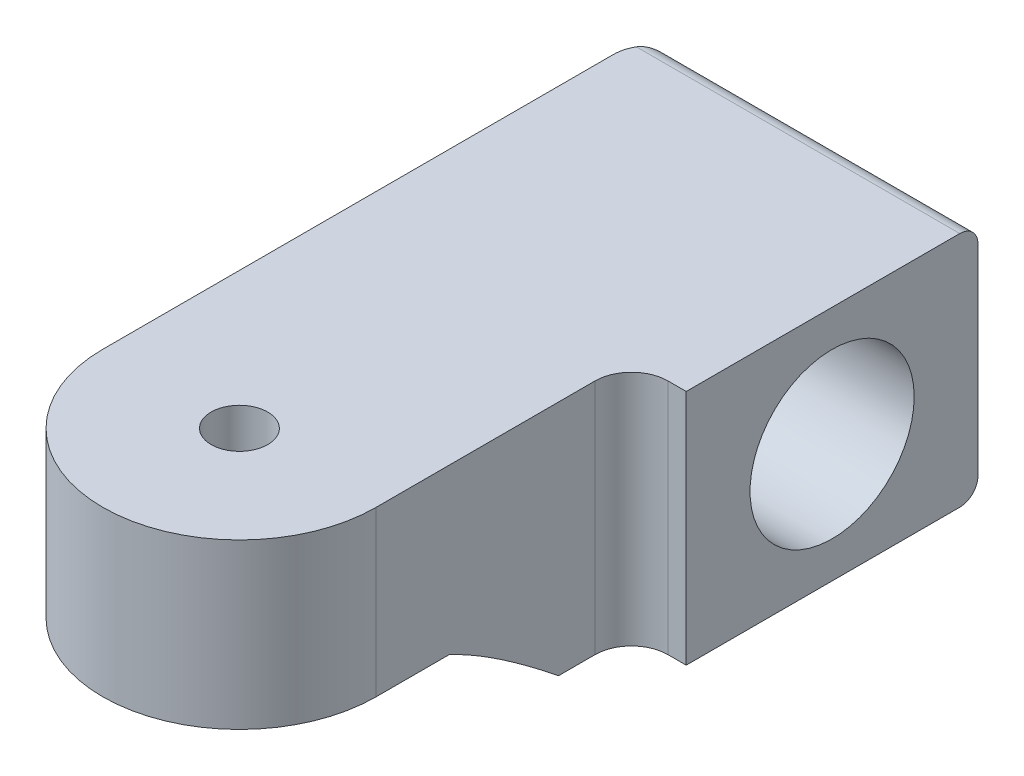
SolidWorks part; units mm, degrees
material "ABS"
ref_plane "前视基准面" through (0, 0, 0) normal (0, 0, 1) x (1, 0, 0)
ref_plane "上视基准面" through (0, 0, 0) normal (0, 1, 0) x (1, 0, 0)
ref_plane "右视基准面" through (0, 0, 0) normal (1, 0, 0) x (0, 0, -1)
sketch "Sketch1" plane through (0, 0, 0) normal (0, 1, 0) x (1, 0, 0)
  line L0 (0, 0) -> (0, 16)
  line L1 (0, 16) -> (-16, 16)
  line L2 (-18, 14) -> (-18, -14)
  line L3 (-18, -14) -> (-3, -14)
  line L4 (-3, -14) -> (-3, -2)
  line L5 (-1, 0) -> (0, 0)
  arc A0 (-3, -2) -> (-1, 0) centre (-1, -2) cw
  arc A1 (-16, 16) -> (-18, 14) centre (-16, 14) ccw
  circle A2 centre (-10.5, -14) radius 7.5
  circle A3 centre (-10.5, -14) radius 1.55
  point P9 (-3, 0)
  point P12 (-18, 16)
  dimension "D5" = 2
  dimension "D6" = 3.1
  dimension "D1" = 16
  dimension "D2" = 18
  dimension "D3" = 30
  dimension "D4" = 3
extrude "Boss-Extrude1" add sketch "Sketch1" along normal mid plane 13 contours A2 L4 A0 L5 L0 L1 A1 L2 region at (-9.414, 0, -4.3355)
extrude "Boss-Extrude2" add sketch "Sketch1<4>" against normal blind 9 from surface contours L3 A2 | L3 A2 region at (-10.5, 0, 17.2958) region at (-10.5, 0, 10.7042) starting at face at (-7.4786, 6.5, -3.0411)
sketch "Sketch1<4>" plane through (0, 0, 0) normal (0, 1, 0) x (1, 0, 0) same geometry as "Sketch1"
sketch "Sketch2" plane through (0, 0, 0) normal (1, 0, 0) x (0, 0, -1)
  line L0 (0, 6.5) -> (16, -6.5)
  circle A0 centre (8, 0) radius 4.5
  dimension "D1" = 9
extrude "Cut-Extrude1" cut sketch "Sketch2" against normal blind 15 contours L0 A0 | L0 A0 region at (0, 1.4823, -9.2043) region at (0, -1.4823, -6.7957)
chamfer "Chamfer1" distance 5 angle 45 1 edges at (-10.5, -6.5, 6.5)
fillet "Fillet1" radius 1 2 edges at (-8, -6.5, -16) (-8, 6.5, -16) tangent propagation no
sketch "Sketch3" plane through (0, -2.5, 0) normal (0, -1, 0) x (1, 0, 0)
  line L144 (-7.4777, 13.9234) -> (-8.0059, 15.1102)
  line L145 (-8.0059, 15.1102) -> (-8.5342, 16.2969)
  line L146 (-8.9225, 16.5791) -> (-10.2144, 16.715)
  line L147 (-10.2144, 16.715) -> (-11.5063, 16.8509)
  line L148 (-11.9448, 16.6557) -> (-12.7085, 15.6049)
  line L149 (-12.7085, 15.6049) -> (-13.4721, 14.554)
  line L150 (-13.5223, 14.0766) -> (-12.9941, 12.8898)
  line L151 (-12.9941, 12.8898) -> (-12.4658, 11.7031)
  line L152 (-12.0775, 11.4209) -> (-10.7856, 11.285)
  line L153 (-10.7856, 11.285) -> (-9.4937, 11.1491)
  line L154 (-9.0552, 11.3443) -> (-8.2915, 12.3951)
  line L155 (-8.2915, 12.3951) -> (-7.5279, 13.446)
  arc A63 (-7.5279, 13.446) -> (-7.4777, 13.9234) centre (-7.9162, 13.7282) ccw
  arc A64 (-8.5342, 16.2969) -> (-8.9225, 16.5791) centre (-8.9727, 16.1018) ccw
  arc A65 (-11.5063, 16.8509) -> (-11.9448, 16.6557) centre (-11.5565, 16.3736) ccw
  arc A66 (-13.4721, 14.554) -> (-13.5223, 14.0766) centre (-13.0838, 14.2718) ccw
  arc A67 (-12.4658, 11.7031) -> (-12.0775, 11.4209) centre (-12.0273, 11.8982) ccw
  arc A68 (-9.4937, 11.1491) -> (-9.0552, 11.3443) centre (-9.4435, 11.6264) ccw
extrude "Cut-Extrude2" cut sketch "Sketch3" against normal blind 3
